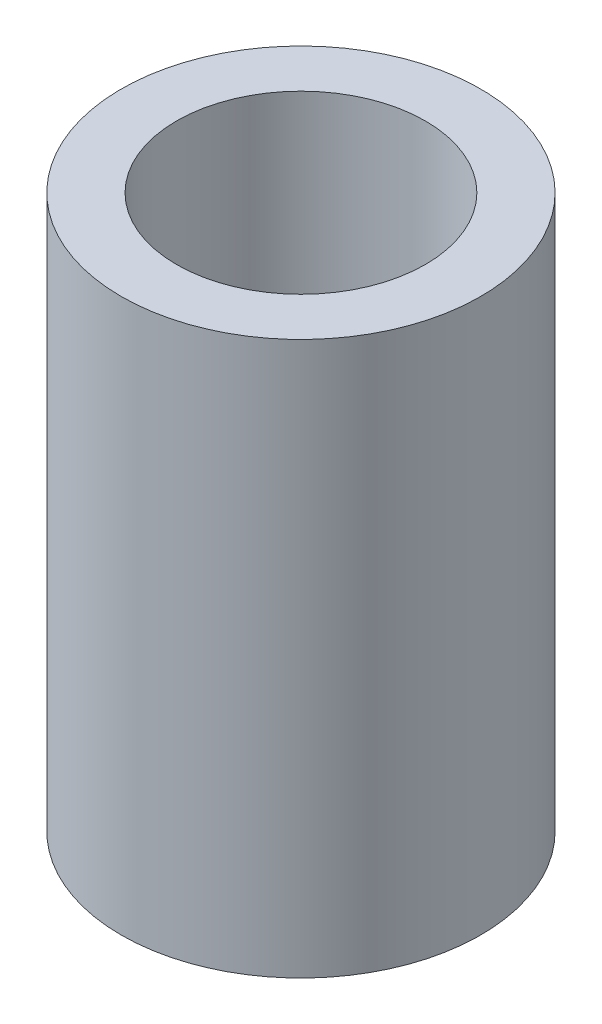
SolidWorks part; units mm, degrees
ref_plane "Front Plane" through (0, 0, 0) normal (0, 0, 1) x (1, 0, 0)
ref_plane "Top Plane" through (0, 0, 0) normal (0, 1, 0) x (1, 0, 0)
ref_plane "Right Plane" through (0, 0, 0) normal (1, 0, 0) x (0, 0, -1)
sketch "Sketch1" plane through (0, 0, 0) normal (0, 1, 0) x (1, 0, 0)
  circle A0 centre (0, 0) radius 2.857
  circle A1 centre (0, 0) radius 4.127
  dimension "D1" = 5.714
  dimension "D2" = 1.27
extrude "Boss-Extrude1" add sketch "Sketch1" along normal blind 12.7
